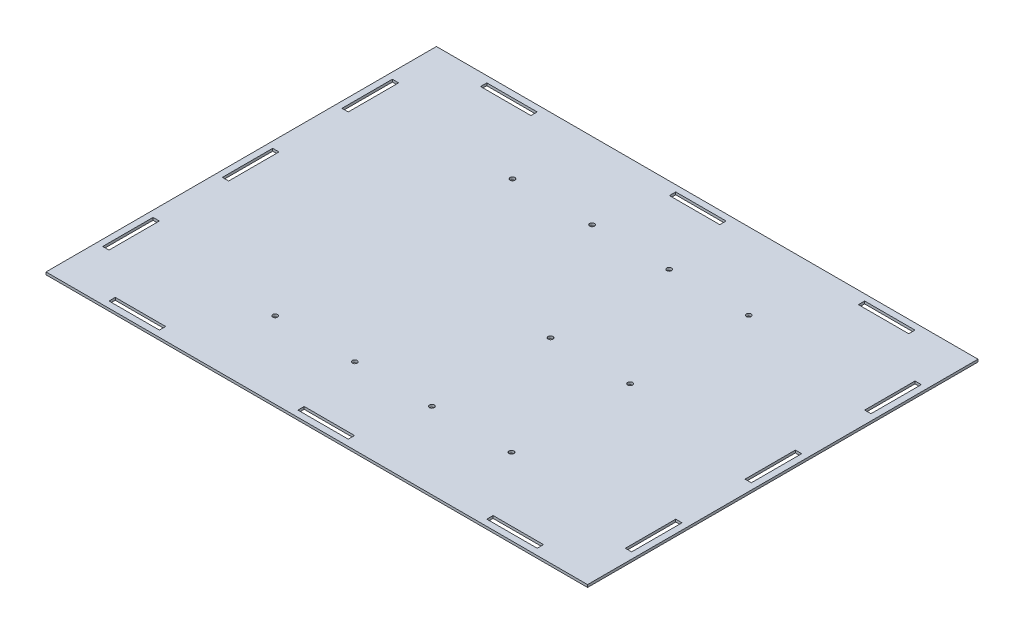
SolidWorks part; units mm, degrees
ref_plane "Front Plane" through (0, 0, 0) normal (0, 0, 1) x (1, 0, 0)
ref_plane "Top Plane" through (0, 0, 0) normal (0, 1, 0) x (1, 0, 0)
ref_plane "Right Plane" through (0, 0, 0) normal (1, 0, 0) x (0, 0, -1)
sketch "Sketch1" plane through (0, 0, 0) normal (0, 1, 0) x (1, 0, 0)
  line L0 (0, 63.5) -> (0, -63.5)
  line L1 (-273.05, 63.5) -> (273.05, 63.5)
  line L2 (-273.05, 63.5) -> (-273.05, -63.5)
  line L4 (273.05, 63.5) -> (273.05, -63.5)
  line L5 (-273.05, -63.5) -> (-273.05, -133.35)
  line L6 (-273.05, -133.35) -> (273.05, -133.35)
  line L7 (273.05, -133.35) -> (273.05, -63.5)
  dimension "D2" = 127
extrude "Boss-Extrude1" add sketch "Sketch1" along normal blind 2.54 contours L2 L0 L1 | L4 L1 L0 region at (-136.525, 0, -57.695)
hole_wizard "#11 (0.191) Diameter Hole2" positions "Sketch10" profile "Sketch9" hole size "#11" standard "ANSI Inch" end condition through all
sketch "Sketch10" plane through (0, 2.54, 0) normal (0, 1, 0) x (1, 0, 0)
  line L0 (-273.05, 63.5) -> (-273.05, -133.35) construction
  line L1 (273.05, 63.5) -> (273.05, -133.35) construction
  point P0 (-119.126, -56.1278)
  point P2 (-38.862, -56.1278)
  point P4 (38.862, -56.1278)
  point P6 (119.126, -56.1278)
  dimension "D1" = 153.924
  dimension "D2" = 153.924
  dimension "D3" = 80.264
  dimension "D4" = 80.264
sketch "Sketch9" plane through (-119.126, 2.54, 56.1278) normal (1, 0, 0) x (0, 0, 1)
  line L0 (0, 0) -> (0, 2.54)
  line L1 (0, 2.54) -> (2.4257, 2.54)
  line L2 (2.4257, 2.54) -> (2.4257, 0)
  line L5 (2.4257, 0) -> (0, 0)
  line L11 (0, -6.35) -> (0, 107.95) construction
  dimension "Thru Hole Dia." = 4.8514
  dimension "Thru Hole Depth" = 2.54
hole_wizard "#11 (0.191) Diameter Hole3" positions "Sketch14" profile "Sketch13" hole size "#11" standard "ANSI Inch" end condition through all
sketch "Sketch14" plane through (0, 2.54, 0) normal (0, 1, 0) x (1, 0, 0)
  point P0 (119.126, 63.5)
  point P2 (38.862, 63.5)
sketch "Sketch13" plane through (119.126, 2.54, -63.5) normal (1, 0, 0) x (0, 0, 1)
  line L0 (0, 0) -> (0, 2.54)
  line L1 (0, 2.54) -> (2.4257, 2.54)
  line L2 (2.4257, 2.54) -> (2.4257, 0)
  line L5 (2.4257, 0) -> (0, 0)
  line L11 (0, -6.35) -> (0, 107.95) construction
  dimension "Thru Hole Dia." = 4.8514
  dimension "Thru Hole Depth" = 2.54
sketch "Sketch17" plane through (0, 2.54, 0) normal (0, 1, 0) x (1, 0, 0)
  line L0 (-273.05, -133.35) -> (-273.05, -63.5) construction
  line L1 (-266.7, -31.75) -> (-260.35, -31.75)
  line L2 (-266.7, -31.75) -> (-266.7, -82.55)
  line L3 (-266.7, -82.55) -> (-260.35, -82.55)
  line L4 (-260.35, -31.75) -> (-260.35, -82.55)
  line L5 (-273.05, -133.35) -> (273.05, -133.35) construction
  line L6 (-215.9, -127) -> (-165.1, -127)
  line L7 (-215.9, -127) -> (-215.9, -120.65)
  line L8 (-215.9, -120.65) -> (-165.1, -120.65)
  line L9 (-165.1, -127) -> (-165.1, -120.65)
  line L10 (273.05, 63.5) -> (273.05, -133.35) construction
  line L11 (165.1, -120.65) -> (215.9, -120.65)
  line L12 (165.1, -120.65) -> (165.1, -127)
  line L13 (165.1, -127) -> (215.9, -127)
  line L14 (215.9, -120.65) -> (215.9, -127)
  line L15 (260.35, -31.75) -> (266.7, -31.75)
  line L16 (260.35, -31.75) -> (260.35, -82.55)
  line L17 (260.35, -82.55) -> (266.7, -82.55)
  line L18 (266.7, -31.75) -> (266.7, -82.55)
  line L19 (-273.05, 63.5) -> (36.4363, 63.5) construction
  line L20 (-25.4, -120.65) -> (25.4, -120.65)
  line L21 (-25.4, -120.65) -> (-25.4, -127)
  line L22 (-25.4, -127) -> (25.4, -127)
  line L23 (25.4, -120.65) -> (25.4, -127)
  line L24 (-266.7, 63.5) -> (-260.35, 63.5)
  line L25 (-266.7, 63.5) -> (-266.7, 38.1)
  line L26 (-266.7, 38.1) -> (-260.35, 38.1)
  line L27 (-260.35, 63.5) -> (-260.35, 38.1)
  line L28 (-273.05, 63.5) -> (-273.05, -133.35) construction
  line L29 (121.5517, 63.5) -> (273.05, 63.5) construction
  line L30 (266.7, 63.5) -> (260.35, 63.5)
  line L31 (266.7, 63.5) -> (266.7, 38.1)
  line L32 (266.7, 38.1) -> (260.35, 38.1)
  line L33 (260.35, 63.5) -> (260.35, 38.1)
  dimension "D1" = 6.35
  dimension "D2" = 6.35
  dimension "D3" = 50.8
  dimension "D4" = 6.35
  dimension "D5" = 50.8
  dimension "D6" = 6.35
  dimension "D7" = 50.8
  dimension "D8" = 50.8
  dimension "D9" = 6.35
  dimension "D10" = 6.35
  dimension "D11" = 50.8
  dimension "D12" = 50.8
  dimension "D13" = 6.35
  dimension "D14" = 6.35
  dimension "D15" = 50.8
  dimension "D16" = 50.8
  dimension "D17" = 50.8
  dimension "D18" = 6.35
  dimension "D19" = 6.35
  dimension "D20" = 139.7
  dimension "D21" = 139.7
  dimension "D22" = 6.35
  dimension "D23" = 6.35
  dimension "D24" = 25.4
  dimension "D25" = 6.35
  dimension "D26" = 6.35
  dimension "D27" = 25.4
extrude "Cut-Extrude12" cut sketch "Sketch17" against normal through all
mirror "Mirror1" about plane through (0, 2.54, -63.5) normal (0, 0, -1) of "Cut-Extrude12", "#11 (0.191) Diameter Hole3", "#11 (0.191) Diameter Hole2", "Boss-Extrude1"
